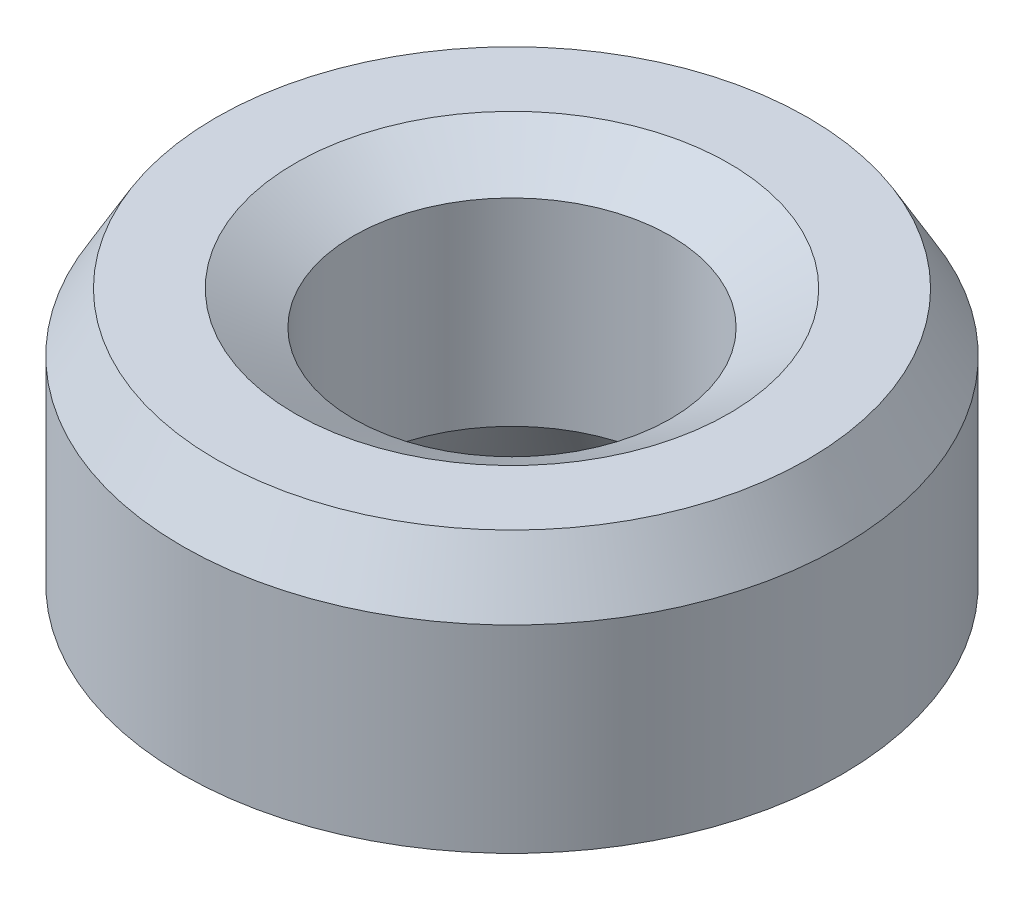
SolidWorks part; units mm, degrees
ref_plane "Front Plane" through (0, 0, 0) normal (0, 0, 1) x (1, 0, 0)
ref_plane "Top Plane" through (0, 0, 0) normal (0, 1, 0) x (1, 0, 0)
ref_plane "Right Plane" through (0, 0, 0) normal (1, 0, 0) x (0, 0, -1)
sketch "Sketch1" plane through (0, 0, 0) normal (0, 1, 0) x (1, 0, 0)
  circle A0 centre (0, 0) radius 7.5
  dimension "SLEEVE_OD" = 15
extrude "Boss-Extrude1" add sketch "Sketch1" along normal blind 6.5938
sketch "Sketch2" plane through (0, 0, 0) normal (0, 1, 0) x (1, 0, 0)
  circle A0 centre (0, 0) radius 3.6059
  dimension "BORE_D" = 7.2118
extrude "Cut-Extrude1" cut sketch "Sketch2" along normal through all
chamfer "Chamfer1" distance 1.3283 angle 30 4 edges at (0, 6.5938, 3.6059) (0, 0, 3.6059) (0, 0, 7.5) (0, 6.5938, 7.5) first distance on face at (0, 6.5938, 3.6059) first distance on face at (0, 0, 3.6059) first distance on face at (0, 6.5938, 7.5)
